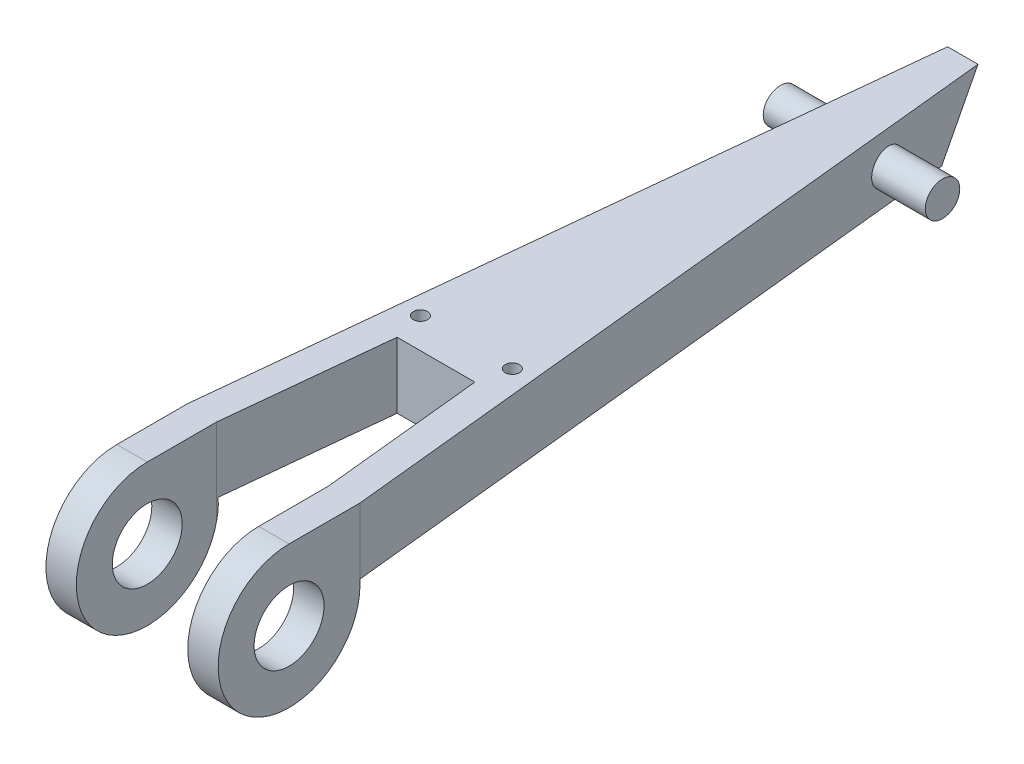
SolidWorks part; units mm, degrees
ref_plane "Front Plane" through (0, 0, 0) normal (0, 0, 1) x (1, 0, 0)
ref_plane "Top Plane" through (0, 0, 0) normal (0, 1, 0) x (1, 0, 0)
ref_plane "Right Plane" through (0, 0, 0) normal (1, 0, 0) x (0, 0, -1)
sketch "Sketch2" plane through (0, 0, 0) normal (1, 0, 0) x (0, 0, -1)
  line L0 (0, 0) -> (4, 6.5)
  line L1 (4, 6.5) -> (-71, 6.5)
  line L2 (0, 0) -> (-64.0179, 0)
  arc A0 (-71, 6.5) -> (-64.0179, 0) centre (-71, -0.5) ccw
  circle A1 centre (-71, -0.5) radius 3.45
  dimension "D4" = 14
  dimension "D5" = 6.9
  dimension "D1" = 75
  dimension "D2" = 4
  dimension "D3" = 6.5
extrude "Boss-Extrude1" add sketch "Sketch2" along normal mid plane 17
sketch "Sketch3" plane through (0, 0, 0) normal (0, -1, 0) x (1, 0, 0)
  line L1 (8.5, 71) -> (-8.5, 71) construction
  line L5 (-1.5, -4) -> (1.5, -4)
  line L6 (8.5, -4) -> (-8.5, -4) construction
  line L7 (8.5, 64) -> (1.5, -4)
  line L8 (-8.5, 64) -> (-1.5, -4)
  line L9 (-8.5, 64) -> (-8.5, -8.9089)
  line L10 (-8.5, -8.9089) -> (8.5, -8.9089)
  line L11 (8.5, -8.9089) -> (8.5, 64)
  line L12 (8.5, 0) -> (-8.5, 0) construction
  line L13 (-5.5, 64.154) -> (-3.8371, 48)
  line L14 (-3.8371, 48) -> (3.8371, 48)
  line L15 (3.8371, 48) -> (5.5, 64.154)
  line L16 (5.5, 64.154) -> (5.5, 78)
  line L17 (8.5, 78) -> (-8.5, 78) construction
  line L18 (5.5, 78) -> (-5.5, 78)
  line L19 (-5.5, 78) -> (-5.5, 64.154)
  line L20 (-8.5, 78) -> (-8.5, 64) construction
  line L21 (8.5, 64) -> (8.5, 78) construction
  point P5 (0, 78)
  point P14 (0, -4)
  point P30 (0, 71)
  dimension "D1" = 3
  dimension "D2" = 8.9089
  dimension "D3" = 30
  dimension "D4" = 3
  dimension "D5" = 3
  dimension "D6" = 3
  dimension "D7" = 3
extrude "Cut-Extrude1" cut sketch "Sketch3" against normal through all both and the other way through all
sketch "Sketch4" plane through (0, 0, 0) normal (1, 0, 0) x (0, 0, -1)
  line L0 (0, 0) -> (4, 6.5) construction
  circle A0 centre (-6, 3.25) radius 1.7
  point P5 (2, 3.25)
  dimension "D2" = 3.4
  dimension "D1" = 10
extrude "Boss-Extrude2" add sketch "Sketch4" along normal mid plane 16
sketch "Sketch5" plane through (0, 6.5, 0) normal (0, 1, 0) x (1, 0, 0)
  line L0 (-3.8371, -48) -> (3.8371, -48) construction
  line L1 (8.5, -64) -> (1.5, 4) construction
  line L2 (-1.5, 4) -> (-8.5, -64) construction
  circle A0 centre (-4.5335, -45) radius 0.7
  circle A1 centre (4.5335, -45) radius 0.7
  dimension "D1" = 1.4
  dimension "D2" = 1.4
  dimension "D3" = 3
  dimension "D5" = 2
  dimension "D6" = 2
extrude "Cut-Extrude2" cut sketch "Sketch5" against normal through all both and the other way through all
